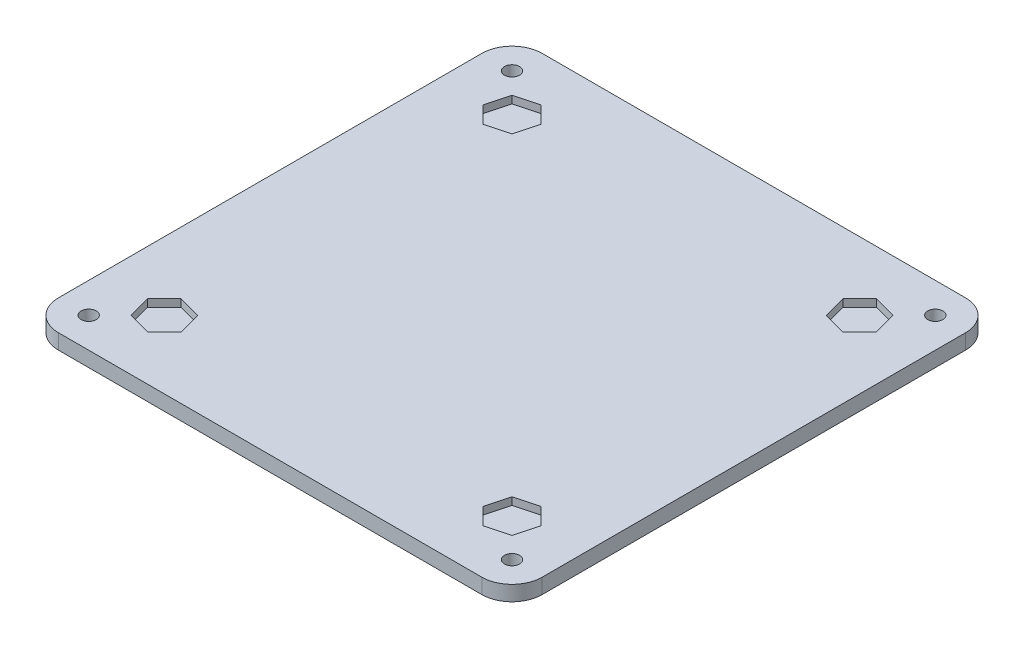
SolidWorks part; units mm, degrees
ref_plane "Front Plane" through (0, 0, 0) normal (0, 0, 1) x (1, 0, 0)
ref_plane "Top Plane" through (0, 0, 0) normal (0, 1, 0) x (1, 0, 0)
ref_plane "Right Plane" through (0, 0, 0) normal (1, 0, 0) x (0, 0, -1)
sketch "Sketch1" plane through (0, 0, 0) normal (0, 1, 0) x (1, 0, 0)
  line L1 (0, 0) -> (203.2, 0)
  line L2 (0, 0) -> (0, 203.2)
  line L3 (0, 203.2) -> (203.2, 203.2)
  line L4 (203.2, 0) -> (203.2, 203.2)
  dimension "D1" = 203.2
  dimension "D2" = 203.2
extrude "Boss-Extrude1" add sketch "Sketch1" along normal blind 6.35
fillet "Fillet1" radius 12.7 4 edges at (0, 3.175, -203.2) (0, 3.175, 0) (203.2, 3.175, 0) (203.2, 3.175, -203.2)
sketch "Sketch2" plane through (0, 0, 0) normal (0, -1, 0) x (1, 0, 0)
  circle A0 centre (12.7, -12.7) radius 3.175
  circle A1 centre (190.5, -12.7) radius 3.175
  circle A2 centre (190.5, -190.5) radius 3.175
  circle A3 centre (12.7, -190.5) radius 3.175
  arc A4 (190.5, -203.2) -> (203.2, -190.5) centre (190.5, -190.5) ccw construction
  arc A5 (12.7, 0) -> (0, -12.7) centre (12.7, -12.7) ccw construction
  dimension "D1" = 6.35
extrude "Cut-Extrude1" cut sketch "Sketch2" against normal through all
sketch "Sketch22" plane through (0, 6.35, 0) normal (0, 1, 0) x (1, 0, 0)
  line L17 (190.5, 203.2) -> (12.7, 203.2) construction
  line L18 (203.2, 12.7) -> (203.2, 190.5) construction
  line L21 (181.6542, 181.6542) -> (172.0521, 184.2271)
  line L22 (172.0521, 184.2271) -> (165.0229, 177.1979)
  line L23 (165.0229, 177.1979) -> (167.5958, 167.5958)
  line L24 (167.5958, 167.5958) -> (177.1979, 165.0229)
  line L25 (177.1979, 165.0229) -> (184.2271, 172.0521)
  line L26 (184.2271, 172.0521) -> (181.6542, 181.6542)
  line L27 (174.625, 174.625) -> (190.5, 190.5) construction
  line L28 (101.6, 203.2) -> (101.6, 0) construction
  line L29 (12.7, 0) -> (190.5, 0) construction
  line L30 (203.2, 101.6) -> (0, 101.6) construction
  line L31 (0, 190.5) -> (0, 12.7) construction
  line L32 (28.575, 174.625) -> (12.7, 190.5) construction
  line L33 (18.9729, 172.0521) -> (21.5458, 181.6542)
  line L34 (26.0021, 165.0229) -> (18.9729, 172.0521)
  line L35 (35.6042, 167.5958) -> (26.0021, 165.0229)
  line L36 (38.1771, 177.1979) -> (35.6042, 167.5958)
  line L37 (31.1479, 184.2271) -> (38.1771, 177.1979)
  line L38 (21.5458, 181.6542) -> (31.1479, 184.2271)
  line L39 (174.625, 28.575) -> (190.5, 12.7) construction
  line L40 (184.2271, 31.1479) -> (181.6542, 21.5458)
  line L41 (177.1979, 38.1771) -> (184.2271, 31.1479)
  line L42 (167.5958, 35.6042) -> (177.1979, 38.1771)
  line L43 (165.0229, 26.0021) -> (167.5958, 35.6042)
  line L44 (172.0521, 18.9729) -> (165.0229, 26.0021)
  line L45 (181.6542, 21.5458) -> (172.0521, 18.9729)
  line L46 (28.575, 28.575) -> (12.7, 12.7) construction
  line L47 (21.5458, 21.5458) -> (31.1479, 18.9729)
  line L48 (31.1479, 18.9729) -> (38.1771, 26.0021)
  line L49 (38.1771, 26.0021) -> (35.6042, 35.6042)
  line L50 (35.6042, 35.6042) -> (26.0021, 38.1771)
  line L51 (26.0021, 38.1771) -> (18.9729, 31.1479)
  line L52 (18.9729, 31.1479) -> (21.5458, 21.5458)
  circle A0 centre (174.625, 174.625) radius 8.609 construction
  circle A1 centre (28.575, 174.625) radius 8.609 construction
  circle A2 centre (174.625, 28.575) radius 8.609 construction
  circle A3 centre (28.575, 28.575) radius 8.609 construction
  dimension "D5" = 17.218
  dimension "D3" = 28.575
  dimension "D4" = 28.575
extrude "Cut-Extrude2" cut sketch "Sketch22" against normal blind 3.175
